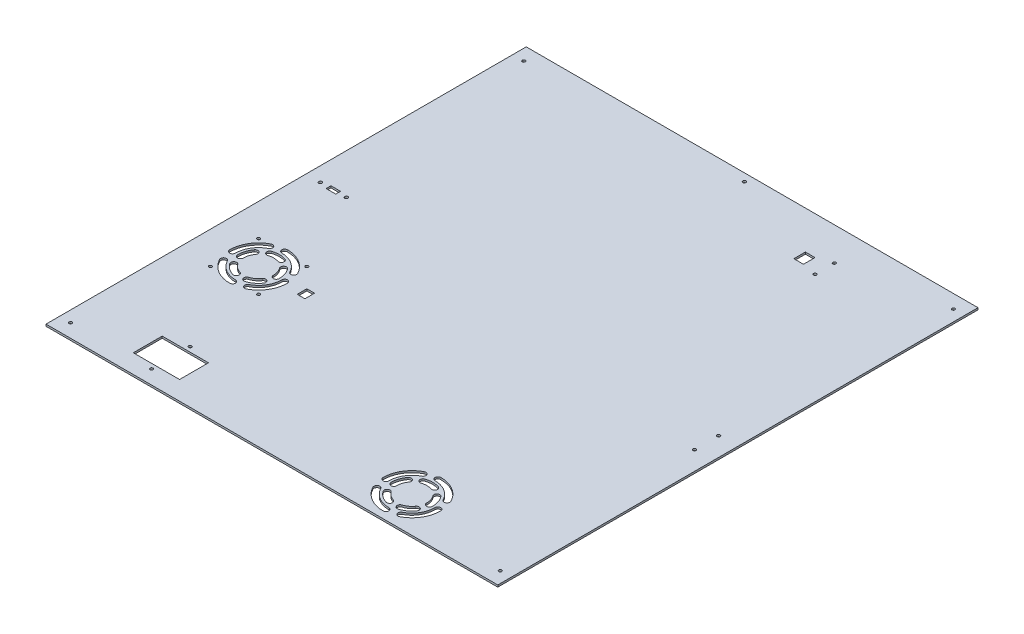
SolidWorks part; units mm, degrees
ref_plane "Alzado" through (0, 0, 0) normal (0, 0, 1) x (1, 0, 0)
ref_plane "Planta" through (0, 0, 0) normal (0, 1, 0) x (1, 0, 0)
ref_plane "Vista lateral" through (0, 0, 0) normal (1, 0, 0) x (0, 0, -1)
sketch "Croquis1" plane through (0, 0, 0) normal (0, 1, 0) x (1, 0, 0)
  line L1 (0, 0) -> (470.5, 0)
  line L2 (0, 0) -> (0, 420)
  line L3 (0, 420) -> (470.5, 420)
  line L4 (470.5, 0) -> (470.5, 420)
  dimension "D1" = 420
  dimension "D2" = 470.5
extrude "Saliente-Extruir1" add sketch "Croquis1" along normal blind 2
sketch "Croquis2" plane through (0, 2, 0) normal (0, 1, 0) x (1, 0, 0)
  line L0 (470.5, 420) -> (0, 420) construction
  line L1 (0, 420) -> (0, 0) construction
  line L2 (235.25, 420) -> (235.25, 0) construction
  line L3 (0, 0) -> (470.5, 0) construction
  line L4 (0, 210) -> (470.5, 210) construction
  line L5 (470.5, 0) -> (470.5, 420) construction
  circle A0 centre (12.5, 405) radius 1.55
  circle A1 centre (458, 405) radius 1.55
  circle A2 centre (458, 15) radius 1.55
  circle A3 centre (12.5, 15) radius 1.55
  dimension "D1" = 3.1
  dimension "D2" = 15
  dimension "D3" = 12.5
extrude "Cortar-Extruir1" cut sketch "Croquis2" against normal up to surface (2 mm away) up to face at (235.25, 0, -210)
sketch "Croquis3" plane through (0, 2, 0) normal (0, 1, 0) x (1, 0, 0)
  line L0 (470, 419.5) -> (0.5, 419.5)
  line L1 (0.5, 419.5) -> (0.5, 0.5)
  line L2 (0.5, 0.5) -> (470, 0.5)
  line L3 (470, 0.5) -> (470, 419.5)
  line L4 (0, 420) -> (0, 0)
  line L5 (0, 0) -> (470.5, 0)
  line L6 (470.5, 0) -> (470.5, 420)
  line L7 (470.5, 420) -> (0, 420)
  line L8 (0, 420) -> (0, 0)
  line L9 (0, 0) -> (470.5, 0)
  line L10 (470.5, 0) -> (470.5, 420)
  line L11 (470.5, 420) -> (0, 420)
  dimension "D1" = 0
  dimension "D2" = 0.5
extrude "Cortar-Extruir2" cut sketch "Croquis3" against normal up to surface (2 mm away) up to face at (12.5, 0, -16.55)
sketch "Croquis4" plane through (0, 2, 0) normal (0, 1, 0) x (1, 0, 0)
  line L0 (0.5, 0.5) -> (470, 0.5) construction
  line L1 (0.5, 419.5) -> (0.5, 0.5) construction
  line L3 (0.5, 419.5) -> (0.5, 0.5) construction
  line L13 (110.5, 201) -> (8.5, 201) construction
  line L14 (110.5, 201) -> (110.5, 125) construction
  line L15 (110.5, 125) -> (8.5, 125) construction
  line L16 (8.5, 201) -> (8.5, 125) construction
  line L17 (59.5, 201) -> (59.5, 125) construction
  line L18 (84.5, 138) -> (34.5, 138) construction
  line L19 (105.5, 105.5) -> (13.5, 105.5) construction
  line L20 (105.5, 105.5) -> (105.5, 220.5) construction
  line L21 (105.5, 220.5) -> (13.5, 220.5) construction
  line L22 (13.5, 105.5) -> (13.5, 220.5) construction
  line L23 (105.5, 105.5) -> (13.5, 220.5) construction
  line L24 (105.5, 220.5) -> (13.5, 105.5) construction
  line L25 (84.5, 138) -> (84.5, 188) construction
  line L26 (84.5, 188) -> (34.5, 188) construction
  line L27 (34.5, 138) -> (34.5, 188) construction
  line L28 (84.5, 138) -> (34.5, 188) construction
  line L29 (84.5, 188) -> (34.5, 138) construction
  line L30 (0.5, 0.5) -> (470, 0.5) construction
  circle A0 centre (343.5, 38) radius 27 construction
  arc A1 (343.5, 65) -> (367.4419, 50.4815) centre (343.5, 38) cw construction
  arc A2 (370.1021, 51.8683) -> (343.5, 68) centre (343.5, 38) ccw
  arc A3 (364.7817, 49.0947) -> (343.5, 62) centre (343.5, 38) ccw
  arc A4 (364.7817, 49.0947) -> (370.1021, 51.8683) centre (367.4419, 50.4815) ccw
  arc A5 (343.5, 68) -> (343.5, 62) centre (343.5, 65) ccw
  arc A6 (354.5947, 16.7183) -> (367.5, 38) centre (343.5, 38) ccw
  arc A7 (354.5947, 16.7183) -> (357.3683, 11.3979) centre (355.9815, 14.0581) ccw
  arc A8 (373.5, 38) -> (367.5, 38) centre (370.5, 38) ccw
  arc A9 (357.3683, 11.3979) -> (373.5, 38) centre (343.5, 38) ccw
  arc A10 (370.5, 38) -> (355.9815, 14.0581) centre (343.5, 38) cw construction
  arc A11 (322.2183, 26.9053) -> (343.5, 14) centre (343.5, 38) ccw
  arc A12 (322.2183, 26.9053) -> (316.8979, 24.1317) centre (319.5581, 25.5185) ccw
  arc A13 (343.5, 8) -> (343.5, 14) centre (343.5, 11) ccw
  arc A14 (316.8979, 24.1317) -> (343.5, 8) centre (343.5, 38) ccw
  arc A15 (343.5, 11) -> (319.5581, 25.5185) centre (343.5, 38) cw construction
  arc A16 (332.4053, 59.2817) -> (319.5, 38) centre (343.5, 38) ccw
  arc A17 (332.4053, 59.2817) -> (329.6317, 64.6021) centre (331.0185, 61.9419) ccw
  arc A18 (313.5, 38) -> (319.5, 38) centre (316.5, 38) ccw
  arc A19 (329.6317, 64.6021) -> (313.5, 38) centre (343.5, 38) ccw
  arc A20 (316.5, 38) -> (331.0185, 61.9419) centre (343.5, 38) cw construction
  circle A21 centre (343.5, 38) radius 18.5 construction
  arc A22 (337.5, 55.5) -> (349.5, 55.5) centre (343.5, 38) cw construction
  arc A23 (350.473, 58.3378) -> (336.527, 58.3378) centre (343.5, 38) ccw
  arc A24 (348.527, 52.6622) -> (338.473, 52.6622) centre (343.5, 38) ccw
  arc A25 (348.527, 52.6622) -> (350.473, 58.3378) centre (349.5, 55.5) ccw
  arc A26 (336.527, 58.3378) -> (338.473, 52.6622) centre (337.5, 55.5) ccw
  arc A27 (358.2894, 49.1141) -> (361.9976, 37.7015) centre (343.5, 38) cw construction
  arc A28 (364.9972, 37.653) -> (360.6877, 50.9164) centre (343.5, 38) ccw
  arc A29 (358.998, 37.7499) -> (355.8911, 47.3118) centre (343.5, 38) ccw
  arc A30 (358.998, 37.7499) -> (364.9972, 37.653) centre (361.9976, 37.7015) ccw
  arc A31 (360.6877, 50.9164) -> (355.8911, 47.3118) centre (358.2894, 49.1141) ccw
  arc A32 (358.6403, 27.3689) -> (348.9321, 20.3155) centre (343.5, 38) cw construction
  arc A33 (349.813, 17.4477) -> (361.0955, 25.645) centre (343.5, 38) ccw
  arc A34 (348.0513, 23.1832) -> (356.1852, 29.0929) centre (343.5, 38) ccw
  arc A35 (348.0513, 23.1832) -> (349.813, 17.4477) centre (348.9321, 20.3155) ccw
  arc A36 (361.0955, 25.645) -> (356.1852, 29.0929) centre (358.6403, 27.3689) ccw
  arc A37 (338.0679, 20.3155) -> (328.3597, 27.3689) centre (343.5, 38) cw construction
  arc A38 (325.9045, 25.645) -> (337.187, 17.4477) centre (343.5, 38) ccw
  arc A39 (330.8148, 29.0929) -> (338.9487, 23.1832) centre (343.5, 38) ccw
  arc A40 (330.8148, 29.0929) -> (325.9045, 25.645) centre (328.3597, 27.3689) ccw
  arc A41 (337.187, 17.4477) -> (338.9487, 23.1832) centre (338.0679, 20.3155) ccw
  arc A42 (325.0024, 37.7015) -> (328.7106, 49.1141) centre (343.5, 38) cw construction
  arc A43 (326.3123, 50.9164) -> (322.0028, 37.653) centre (343.5, 38) ccw
  arc A44 (331.1089, 47.3118) -> (328.002, 37.7499) centre (343.5, 38) ccw
  arc A45 (331.1089, 47.3118) -> (326.3123, 50.9164) centre (328.7106, 49.1141) ccw
  arc A46 (322.0028, 37.653) -> (328.002, 37.7499) centre (325.0024, 37.7015) ccw
  circle A47 centre (84.5, 188) radius 1.55
  circle A48 centre (84.5, 138) radius 1.55
  circle A57 centre (34.5, 138) radius 1.55
  circle A68 centre (34.5, 188) radius 1.55
  circle A69 centre (59.5, 163) radius 27 construction
  arc A84 (59.5, 190) -> (83.4419, 175.4815) centre (59.5, 163) cw construction
  circle A94 centre (458, 405) radius 1.55 construction
  arc A98 (86.1021, 176.8683) -> (59.5, 193) centre (59.5, 163) ccw
  arc A103 (80.7817, 174.0947) -> (59.5, 187) centre (59.5, 163) ccw
  arc A124 (80.7817, 174.0947) -> (86.1021, 176.8683) centre (83.4419, 175.4815) ccw
  arc A129 (59.5, 193) -> (59.5, 187) centre (59.5, 190) ccw
  circle A143 centre (110.5, 201) radius 1.55 construction
  circle A144 centre (8.5, 201) radius 1.55 construction
  circle A145 centre (8.5, 125) radius 1.55 construction
  circle A146 centre (110.5, 125) radius 1.55 construction
  circle A147 centre (105.5, 220.5) radius 1.55 construction
  circle A148 centre (13.5, 220.5) radius 1.55 construction
  circle A149 centre (13.5, 105.5) radius 1.55 construction
  circle A150 centre (105.5, 105.5) radius 1.55 construction
  arc A154 (86.5, 163) -> (71.9815, 139.0581) centre (59.5, 163) cw construction
  arc A159 (73.3683, 136.3979) -> (89.5, 163) centre (59.5, 163) ccw
  arc A164 (70.5947, 141.7183) -> (83.5, 163) centre (59.5, 163) ccw
  circle A165 centre (59.5, 163) radius 18.5 construction
  arc A166 (53.5, 180.5) -> (65.5, 180.5) centre (59.5, 163) cw construction
  arc A167 (66.473, 183.3378) -> (52.527, 183.3378) centre (59.5, 163) ccw
  arc A168 (64.527, 177.6622) -> (54.473, 177.6622) centre (59.5, 163) ccw
  arc A169 (64.527, 177.6622) -> (66.473, 183.3378) centre (65.5, 180.5) ccw
  arc A170 (52.527, 183.3378) -> (54.473, 177.6622) centre (53.5, 180.5) ccw
  arc A171 (70.5947, 141.7183) -> (73.3683, 136.3979) centre (71.9815, 139.0581) ccw
  arc A172 (89.5, 163) -> (83.5, 163) centre (86.5, 163) ccw
  arc A173 (59.5, 136) -> (35.5581, 150.5185) centre (59.5, 163) cw construction
  arc A174 (32.8979, 149.1317) -> (59.5, 133) centre (59.5, 163) ccw
  arc A175 (38.2183, 151.9053) -> (59.5, 139) centre (59.5, 163) ccw
  arc A176 (38.2183, 151.9053) -> (32.8979, 149.1317) centre (35.5581, 150.5185) ccw
  arc A177 (59.5, 133) -> (59.5, 139) centre (59.5, 136) ccw
  arc A178 (32.5, 163) -> (47.0185, 186.9419) centre (59.5, 163) cw construction
  arc A179 (45.6317, 189.6021) -> (29.5, 163) centre (59.5, 163) ccw
  arc A180 (48.4053, 184.2817) -> (35.5, 163) centre (59.5, 163) ccw
  arc A181 (48.4053, 184.2817) -> (45.6317, 189.6021) centre (47.0185, 186.9419) ccw
  arc A182 (29.5, 163) -> (35.5, 163) centre (32.5, 163) ccw
  circle A183 centre (59.5, 163) radius 18.5 construction
  arc A184 (74.2894, 174.1141) -> (77.9976, 162.7015) centre (59.5, 163) cw construction
  arc A185 (80.9972, 162.653) -> (76.6877, 175.9164) centre (59.5, 163) ccw
  arc A186 (74.998, 162.7499) -> (71.8911, 172.3118) centre (59.5, 163) ccw
  arc A187 (74.998, 162.7499) -> (80.9972, 162.653) centre (77.9976, 162.7015) ccw
  arc A188 (76.6877, 175.9164) -> (71.8911, 172.3118) centre (74.2894, 174.1141) ccw
  circle A189 centre (59.5, 163) radius 18.5 construction
  arc A190 (74.6403, 152.3689) -> (64.9321, 145.3155) centre (59.5, 163) cw construction
  arc A191 (65.813, 142.4477) -> (77.0955, 150.645) centre (59.5, 163) ccw
  arc A192 (64.0513, 148.1832) -> (72.1852, 154.0929) centre (59.5, 163) ccw
  arc A193 (64.0513, 148.1832) -> (65.813, 142.4477) centre (64.9321, 145.3155) ccw
  arc A194 (77.0955, 150.645) -> (72.1852, 154.0929) centre (74.6403, 152.3689) ccw
  circle A195 centre (59.5, 163) radius 18.5 construction
  arc A196 (54.0679, 145.3155) -> (44.3597, 152.3689) centre (59.5, 163) cw construction
  arc A197 (41.9045, 150.645) -> (53.187, 142.4477) centre (59.5, 163) ccw
  arc A198 (46.8148, 154.0929) -> (54.9487, 148.1832) centre (59.5, 163) ccw
  arc A199 (46.8148, 154.0929) -> (41.9045, 150.645) centre (44.3597, 152.3689) ccw
  arc A200 (53.187, 142.4477) -> (54.9487, 148.1832) centre (54.0679, 145.3155) ccw
  circle A201 centre (59.5, 163) radius 18.5 construction
  arc A202 (41.0024, 162.7015) -> (44.7106, 174.1141) centre (59.5, 163) cw construction
  arc A203 (42.3123, 175.9164) -> (38.0028, 162.653) centre (59.5, 163) ccw
  arc A204 (47.1089, 172.3118) -> (44.002, 162.7499) centre (59.5, 163) ccw
  arc A205 (47.1089, 172.3118) -> (42.3123, 175.9164) centre (44.7106, 174.1141) ccw
  arc A206 (38.0028, 162.653) -> (44.002, 162.7499) centre (41.0024, 162.7015) ccw
  point P9 (357.5, 61.0868)
  point P19 (366.5868, 24)
  point P26 (329.5, 14.9132)
  point P33 (320.4132, 52)
  point P38 (343.5, 38)
  point P40 (343.5, 56.5)
  point P48 (361.0945, 43.7168)
  point P51 (59.5, 163)
  point P57 (354.374, 23.0332)
  point P64 (332.626, 23.0332)
  point P71 (325.9055, 43.7168)
  point P76 (343.5, 38)
  point P88 (73.5, 186.0868)
  point P100 (82.5868, 149)
  point P107 (45.5, 139.9132)
  point P114 (36.4132, 177)
  point P119 (59.5, 181.5)
  point P125 (302, 221.5)
  point P129 (77.0945, 168.7168)
  point P137 (70.374, 148.0332)
  point P147 (48.626, 148.0332)
  point P157 (41.9055, 168.7168)
  point P171 (59.5, 163)
  point P183 (302, 221.5)
  dimension "D1" = 54
  dimension "D7" = 37
  dimension "D13" = 54
  dimension "D18" = 6
  dimension "D19" = 105
  dimension "D20" = 105
  dimension "D28" = 3.1
  dimension "D16" = 37
  dimension "D2" = 37.5
  dimension "D3" = 343
  dimension "D4" = 28
  dimension "D5" = 6
  dimension "D8" = 12
  dimension "D9" = 6
  dimension "D11" = 50
  dimension "D12" = 50
  dimension "D14" = 28
  dimension "D15" = 6
  dimension "D17" = 12
  dimension "D26" = 102
  dimension "D27" = 76
  dimension "D31" = 92
  dimension "D32" = 115
  dimension "D6" = 4
  dimension "D10" = 5
extrude "Cortar-Extruir3" cut sketch "Croquis4" against normal up to surface (2 mm away) up to face at (12.5, 0, -406.55)
sketch "Croquis5" plane through (0, 0, 0) normal (0, -1, 0) x (1, 0, 0)
  line L0 (120, -35.5) -> (72, -35.5) construction
  line L1 (120, -50.5) -> (72, -50.5)
  line L2 (120, -50.5) -> (120, -20.5)
  line L3 (120, -20.5) -> (72, -20.5)
  line L4 (72, -50.5) -> (72, -20.5)
  line L5 (470, -0.5) -> (470, -419.5) construction
  line L6 (0.5, -0.5) -> (470, -0.5) construction
  circle A1 centre (96, -15.5) radius 1.55
  circle A2 centre (96, -55.5) radius 1.55
  dimension "D3" = 3.1
  dimension "D1" = 48
  dimension "D2" = 30
  dimension "D4" = 5
  dimension "D5" = 24
  dimension "D6" = 350
  dimension "D7" = 20
extrude "Cortar-Extruir4" cut sketch "Croquis5" against normal up to surface (2 mm away) up to face at (326.8437, 2, -43.412)
sketch "Croquis8" plane through (0, 0, 0) normal (0, -1, 0) x (1, 0, 0)
  line L1 (470, -419.5) -> (0.5, -419.5)
  line L2 (470, -419.5) -> (470, -449.5)
  line L3 (470, -449.5) -> (0.5, -449.5)
  line L4 (0.5, -419.5) -> (0.5, -449.5)
  dimension "D1" = 30
extrude "Saliente-Extruir2" add sketch "Croquis8" against normal up to surface (2 mm away) up to face at (96, 2, -57.05)
sketch "Croquis10" plane through (0, 0, 0) normal (0, -1, 0) x (1, 0, 0)
  circle A0 centre (458, -405) radius 1.75
  circle A1 centre (12.5, -405) radius 1.75
  dimension "D1" = 3.5
  dimension "D2" = 3.5
extrude "Saliente-Extruir3" add sketch "Croquis10" against normal up to surface (2 mm away) up to face at (96, 2, -57.05)
sketch "Croquis11" plane through (0, 0, -449.5) normal (0, 0, -1) x (-1, 0, 0)
  line L4 (-0.5, 2) -> (-470, 2)
  line L5 (-470, 2) -> (-470, 0)
  line L6 (-470, 0) -> (-0.5, 0)
  line L7 (-0.5, 0) -> (-0.5, 2)
  line L8 (-0.5, 2) -> (-470, 2)
  line L9 (-470, 2) -> (-470, 0)
  line L10 (-470, 0) -> (-0.5, 0)
  line L11 (-0.5, 0) -> (-0.5, 2)
  dimension "D1" = 0
extrude "Saliente-Extruir4" add sketch "Croquis11" along normal blind 50
sketch "Croquis12" plane through (0, 0, 0) normal (0, -1, 0) x (1, 0, 0)
  line L0 (470, -0.5) -> (470, -499.5) construction
  line L1 (0.5, -499.5) -> (0.5, -0.5) construction
  line L3 (470, -499.5) -> (0.5, -499.5) construction
  circle A0 centre (458, -485) radius 1.55
  circle A1 centre (12.5, -485) radius 1.55
  dimension "D1" = 3.1
  dimension "D2" = 3.1
  dimension "D3" = 12
  dimension "D4" = 12
  dimension "D5" = 14.5
  dimension "D6" = 14.5
extrude "Cortar-Extruir8" cut sketch "Croquis12" against normal up to surface (2 mm away) up to face at (96, 2, -57.05)
sketch "Croquis13" plane through (0, 0, 0) normal (0, -1, 0) x (1, 0, 0)
  line L0 (470, -0.5) -> (470, -499.5) construction
  line L1 (470, -499.5) -> (0.5, -499.5) construction
  line L3 (340, -459.5) -> (330, -459.5)
  line L4 (340, -459.5) -> (340, -447.5)
  line L5 (340, -447.5) -> (330, -447.5)
  line L6 (330, -459.5) -> (330, -447.5)
  circle A0 centre (355, -464.5) radius 1.55
  circle A1 centre (355, -444.5) radius 1.55
  dimension "D1" = 3.1
  dimension "D2" = 20
  dimension "D3" = 115
  dimension "D4" = 35
  dimension "D5" = 10
  dimension "D6" = 12
  dimension "D7" = 40
  dimension "D8" = 140
extrude "Cortar-Extruir9" cut sketch "Croquis13" against normal up to surface (2 mm away) up to face at (458, 2, -486.55)
sketch "Croquis14" plane through (0, 0, 0) normal (0, -1, 0) x (1, 0, 0)
  line L1 (112.5, -168) -> (104.5, -168)
  line L2 (112.5, -168) -> (112.5, -158)
  line L3 (112.5, -158) -> (104.5, -158)
  line L4 (104.5, -168) -> (104.5, -158)
  circle A0 centre (84.5, -188) radius 1.55 construction
  dimension "D1" = 8
  dimension "D2" = 10
  dimension "D3" = 20
  dimension "D4" = 20
extrude "Cortar-Extruir10" cut sketch "Croquis14" against normal up to surface (2 mm away) up to face at (355, 2, -466.05)
sketch "Croquis15" plane through (0, 0, 0) normal (0, -1, 0) x (1, 0, 0)
  line L0 (470, -0.5) -> (470, -499.5) construction
  line L2 (470, -499.5) -> (0.5, -499.5) construction
  circle A0 centre (450, -249.5) radius 1.6
  circle A1 centre (450, -224.5) radius 1.6
  dimension "D1" = 3.2
  dimension "D2" = 25
  dimension "D3" = 20
  dimension "D4" = 250
extrude "Cortar-Extruir11" cut sketch "Croquis15" against normal up to surface (2 mm away) up to face at (108.5, 2, -163)
sketch "Croquis16" plane through (0, 0, 0) normal (0, -1, 0) x (1, 0, 0)
  line L4 (0.5, -0.5) -> (470, -0.5) construction
  line L5 (0.5, -499.5) -> (0.5, -0.5) construction
  line L6 (470, -0.5) -> (470, -499.5) construction
  line L7 (470, -499.5) -> (0.5, -499.5) construction
  line L8 (1, -1) -> (1, -499)
  line L9 (1, -499) -> (469.5, -499)
  line L10 (469.5, -499) -> (469.5, -1)
  line L11 (469.5, -1) -> (1, -1)
  line L12 (1, -1) -> (1, -499)
  line L13 (1, -499) -> (469.5, -499)
  line L14 (469.5, -499) -> (469.5, -1)
  line L15 (469.5, -1) -> (1, -1)
  line L16 (0.5, -0.5) -> (470, -0.5)
  line L17 (0.5, -499.5) -> (0.5, -0.5)
  line L18 (470, -0.5) -> (470, -499.5)
  line L19 (470, -499.5) -> (0.5, -499.5)
  dimension "D1" = 0.5
extrude "Cortar-Extruir12" cut sketch "Croquis16" against normal up to surface (2 mm away) up to face at (450, 2, -251.1)
sketch "Croquis17" plane through (0, 2, 0) normal (0, 1, 0) x (1, 0, 0)
  line L0 (469.5, 499) -> (1, 499) construction
  line L1 (1, 499) -> (1, 1) construction
  circle A0 centre (235.25, 491) radius 1.6
  dimension "D1" = 3.2
  dimension "D2" = 8
  dimension "D3" = 234.25
extrude "Cortar-Extruir13" cut sketch "Croquis17" against normal up to surface (2 mm away) up to face at (12.5, 0, -16.55)
sketch "Croquis18" plane through (0, 0, 0) normal (0, -1, 0) x (1, 0, 0)
  line L0 (34.5, -270.5) -> (16, -270.5) construction
  line L1 (34.5, -273) -> (24.5, -273)
  line L2 (34.5, -273) -> (34.5, -268)
  line L3 (34.5, -268) -> (24.5, -268)
  line L4 (24.5, -273) -> (24.5, -268)
  line L5 (34.5, -270.5) -> (43, -270.5) construction
  line L6 (29.5, -273) -> (29.5, -268) construction
  line L7 (1, -1) -> (1, -499) construction
  line L9 (72, -50.5) -> (120, -50.5) construction
  circle A0 centre (16, -270.5) radius 1.65
  circle A1 centre (43, -270.5) radius 1.65
  dimension "D3" = 3.3
  dimension "D4" = 3.3
  dimension "D1" = 10
  dimension "D2" = 5
  dimension "D5" = 27
  dimension "D6" = 13.5
  dimension "D7" = 15
  dimension "D8" = 220
extrude "Cortar-Extruir14" cut sketch "Croquis18" against normal up to surface (2 mm away) up to face at (235.25, 2, -489.4)
